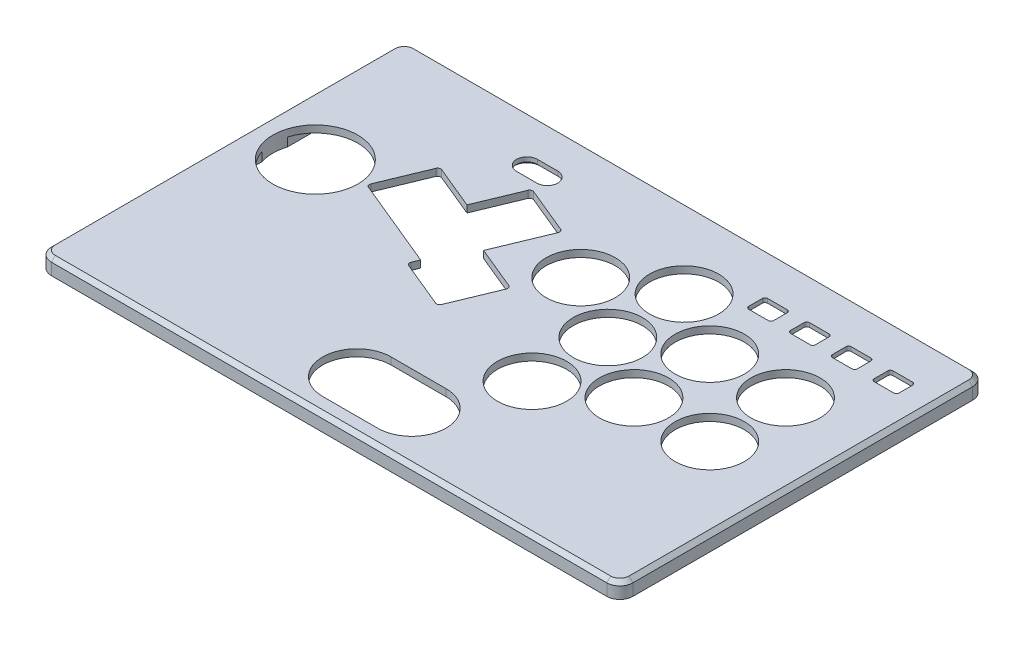
SolidWorks part; units mm, degrees
ref_plane "Front Plane" through (0, 0, 0) normal (0, 0, 1) x (1, 0, 0)
ref_plane "Top Plane" through (0, 0, 0) normal (0, 1, 0) x (1, 0, 0)
ref_plane "Right Plane" through (0, 0, 0) normal (1, 0, 0) x (0, 0, -1)
sketch "Sketch1" plane through (0, 0, 0) normal (0, 1, 0) x (1, 0, 0)
  line L1 (0, 0) -> (222.53, 0)
  line L2 (0, 0) -> (0, 140)
  line L3 (0, 140) -> (222.53, 140)
  line L4 (222.53, 0) -> (222.53, 140)
  line L5 (217.53, 140) -> (50.88, 140) construction
  line L6 (222.53, 5) -> (222.53, 135) construction
extrude "Top Plate" add sketch "Sketch1" along normal blind 6
fillet "Corner Fillet" radius 5 4 edges at (0, 3, -140) (0, 3, 0) (222.53, 3, -140) (222.53, 3, 0)
hole_wizard "M3 Clearance Hole1" positions "3DSketch1" profile "Sketch3" hole size "M3" standard "ANSI Metric"
sketch3d "3DSketch1"
  line L0 (5, 0, 0) -> (217.53, 0, 0) construction
  line L1 (222.53, 0, -5) -> (222.53, 0, -135) construction
  line L2 (217.53, 0, -140) -> (5, 0, -140) construction
  line L3 (0, 0, -135) -> (0, 0, -5) construction
  point P0 (217.03, 0, -5.5)
  point P2 (217.03, 0, -134.5)
  point P4 (5.5, 0, -134.5)
  point P6 (5.5, 0, -5.5)
  dimension "D1" = 5.5
  dimension "D2" = 5.5
  dimension "D3" = 5.5
  dimension "D4" = 5.5
  dimension "D5" = 5.5
  dimension "D6" = 5.5
  dimension "D7" = 5.5
  dimension "D8" = 5.5
sketch "Sketch3" plane through (217.03, 0, -5.5) normal (1, 0, 0) x (0, 0, -1)
  line L0 (0, 0) -> (0, 5.25)
  line L1 (0, 5.25) -> (1.7, 4.2285)
  line L2 (1.7, 4.2285) -> (1.7, 0)
  line L5 (1.7, 0) -> (0, 0)
  line L10 (0, 5.25) -> (-1.7, 4.2285) construction
  line L11 (0, -6.35) -> (0, 107.95) construction
  dimension "Hole Dia." = 3.4
  dimension "Hole Depth" = 5.25
  dimension "Drill Angle" = 118
sketch "Sketch4" plane through (0, 6, 0) normal (0, -1, 0) x (-1, 0, 0)
  line L0 (-94.0588, 59.555) -> (-76.4589, 66.8451) construction
  line L1 (-94.0588, 59.555) -> (-101.349, 77.1549) construction
  line L2 (-76.4589, 66.8451) -> (-77.9897, 70.5406) construction
  line L3 (-101.349, 77.1549) -> (-83.7491, 84.445) construction
  line L4 (-94.0588, 59.555) -> (-83.7491, 84.445) construction
  line L5 (-76.4589, 66.8451) -> (-101.349, 77.1549) construction
  line L6 (-77.9897, 70.5406) -> (-60.3898, 77.8307) construction
  line L7 (-83.7491, 84.445) -> (-85.2798, 88.1405) construction
  line L8 (-60.3898, 77.8307) -> (-67.6799, 95.4306) construction
  line L9 (-85.2798, 88.1405) -> (-67.6799, 95.4306) construction
  line L10 (-77.9897, 70.5406) -> (-67.6799, 95.4306) construction
  line L11 (-60.3898, 77.8307) -> (-85.2798, 88.1405) construction
  line L12 (-60.3898, 77.8307) -> (-42.7899, 85.1209) construction
  line L14 (-42.7899, 85.1209) -> (-50.08, 102.7208) construction
  line L15 (-67.6799, 95.4306) -> (-50.08, 102.7208) construction
  line L16 (-60.3898, 77.8307) -> (-50.08, 102.7208) construction
  line L17 (-42.7899, 85.1209) -> (-67.6799, 95.4306) construction
  line L19 (-67.6799, 95.4306) -> (-74.97, 113.0306) construction
  line L20 (-85.2798, 88.1405) -> (-92.5699, 105.7404) construction
  line L21 (-74.97, 113.0306) -> (-92.5699, 105.7404) construction
  line L22 (-67.6799, 95.4306) -> (-92.5699, 105.7404) construction
  line L23 (-85.2798, 88.1405) -> (-74.97, 113.0306) construction
  line L24 (-5, 0) -> (-217.53, 0) construction
  line L25 (-59.9305, 76.7221) -> (-42.3306, 84.0122)
  line L26 (-41.6812, 85.5801) -> (-48.9713, 103.18)
  line L27 (-67.0304, 96.9985) -> (-50.5392, 103.8294)
  line L28 (-67.0304, 96.9985) -> (-73.8613, 113.4898)
  line L29 (-75.4292, 114.1392) -> (-93.0291, 106.8491)
  line L30 (-86.3884, 87.6813) -> (-93.6786, 105.2812)
  line L31 (-85.3169, 85.0944) -> (-86.3884, 87.6813)
  line L32 (-101.8082, 78.2635) -> (-85.3169, 85.0944)
  line L33 (-95.1675, 59.0958) -> (-102.4576, 76.6957)
  line L34 (-93.5996, 58.4463) -> (-75.9997, 65.7365)
  line L35 (-75.3503, 67.3043) -> (-76.4218, 69.8912)
  line L36 (-76.4218, 69.8912) -> (-59.9305, 76.7221)
  line L37 (-66.5712, 95.8899) -> (-74.3206, 114.5984) construction
  line L38 (-68.1391, 96.5393) -> (-49.4305, 104.2886) construction
  line L39 (-74.3206, 114.5984) -> (-94.1378, 106.3899) construction
  line L40 (-86.3884, 87.6813) -> (-94.1378, 106.3899) construction
  line L41 (-102.9168, 77.8043) -> (-85.3169, 85.0944) construction
  line L42 (-94.7083, 57.9871) -> (-102.9168, 77.8043) construction
  line L43 (-94.7083, 57.9871) -> (-74.8911, 66.1957) construction
  line L44 (-74.8911, 66.1957) -> (-76.4218, 69.8912) construction
  line L45 (-59.9305, 76.7221) -> (-41.222, 84.4714) construction
  line L46 (-41.222, 84.4714) -> (-49.4305, 104.2886) construction
  line L47 (-123.9039, 19) -> (-102.9039, 19) construction
  line L48 (-123.9039, 32.1) -> (-102.9039, 32.1)
  line L49 (-123.9039, 5.9) -> (-102.9039, 5.9)
  circle A0 centre (-23, 83.0083) radius 16.25
  circle A1 centre (-137.9339, 51) radius 13.25
  circle A2 centre (-162.9339, 65) radius 13.25
  circle A3 centre (-191.9339, 65) radius 13.25
  circle A4 centre (-191.9339, 94) radius 13.25
  circle A5 centre (-162.9339, 94) radius 13.25
  circle A6 centre (-137.9339, 80) radius 13.25
  circle A7 centre (-138.1143, 108.9994) radius 13.25
  circle A8 centre (-112.9159, 94.6459) radius 13.25
  arc A9 (-93.0291, 106.8491) -> (-93.6786, 105.2812) centre (-92.5699, 105.7404) ccw
  arc A10 (-101.8082, 78.2635) -> (-102.4576, 76.6957) centre (-101.349, 77.1549) ccw
  arc A11 (-95.1675, 59.0958) -> (-93.5996, 58.4463) centre (-94.0588, 59.555) ccw
  arc A12 (-75.9997, 65.7365) -> (-75.3503, 67.3043) centre (-76.4589, 66.8451) ccw
  arc A13 (-42.3306, 84.0122) -> (-41.6812, 85.5801) centre (-42.7899, 85.1209) ccw
  arc A14 (-73.8613, 113.4898) -> (-75.4292, 114.1392) centre (-74.97, 113.0306) ccw
  arc A15 (-48.9713, 103.18) -> (-50.5392, 103.8294) centre (-50.08, 102.7208) ccw
  arc A16 (-123.9039, 32.1) -> (-123.9039, 5.9) centre (-123.9039, 19) ccw
  arc A17 (-102.9039, 5.9) -> (-102.9039, 32.1) centre (-102.9039, 19) ccw
  point P28 (-88.9039, 72)
  point P29 (-72.8348, 82.9856)
  point P30 (-55.2349, 90.2758)
  point P35 (-80.1249, 100.5855)
  point P90 (-113.4039, 19)
  point P96 (-89.8039, 19)
  point P97 (-137.0039, 19)
  dimension "D1" = 32.5
  dimension "D2" = 26.5
  dimension "D6" = 1.2
  dimension "D8" = 13.1
  dimension "D3" = 22.5
  dimension "D4" = 19.05
  dimension "D5" = 1.2
  dimension "D7" = 47.2
extrude "Primary Buttons" cut sketch "Sketch4" along normal blind 10 contours A15 L26 A13 L25 L36 L35 A12 L34 A11 L33 A10 L32 L31 L30 A9 L29 A14 L28 L27 | A0 | A8 | A7 | A5 | A4 | A6 | A1 | A2 | A3 | A17 L49 A16 L48 region at (74.3536, 6, -86.5154) region at (113.4039, 6, -19) region at (23, 6, -83.0083) region at (137.9339, 6, -51) region at (162.9339, 6, -65) region at (191.9339, 6, -65) region at (191.9339, 6, -94) region at (162.9339, 6, -94) region at (137.9339, 6, -80) region at (138.1143, 6, -108.9994) region at (112.9159, 6, -94.6459)
sketch "Sketch5" plane through (0, 0, 0) normal (0, -1, 0) x (1, 0, 0)
  line L2 (154.55, -122.52) -> (154.55, -117.32)
  line L3 (155.55, -116.32) -> (163.05, -116.32)
  line L4 (164.05, -122.52) -> (164.05, -117.32)
  line L5 (154.55, -123.52) -> (164.05, -116.32) construction
  line L6 (154.55, -116.32) -> (164.05, -123.52) construction
  line L7 (155.55, -123.52) -> (163.05, -123.52)
  line L8 (170.55, -122.52) -> (170.55, -117.32)
  line L9 (171.55, -116.32) -> (179.05, -116.32)
  line L10 (180.05, -122.52) -> (180.05, -117.32)
  line L11 (171.55, -123.52) -> (179.05, -123.52)
  line L12 (170.55, -123.52) -> (180.05, -116.32) construction
  line L13 (170.55, -116.32) -> (180.05, -123.52) construction
  line L14 (186.55, -122.52) -> (186.55, -117.32)
  line L15 (187.55, -116.32) -> (195.05, -116.32)
  line L16 (196.05, -122.52) -> (196.05, -117.32)
  line L17 (187.55, -123.52) -> (195.05, -123.52)
  line L18 (186.55, -123.52) -> (196.05, -116.32) construction
  line L19 (186.55, -116.32) -> (196.05, -123.52) construction
  line L20 (202.55, -122.52) -> (202.55, -117.32)
  line L21 (203.55, -116.32) -> (211.05, -116.32)
  line L22 (212.05, -122.52) -> (212.05, -117.32)
  line L23 (203.55, -123.52) -> (211.05, -123.52)
  line L24 (202.55, -123.52) -> (212.05, -116.32) construction
  line L25 (202.55, -116.32) -> (212.05, -123.52) construction
  line L26 (159.3, -119.92) -> (160, -119.92) construction
  arc A0 (163.05, -123.52) -> (164.05, -122.52) centre (163.05, -122.52) ccw
  arc A1 (155.55, -123.52) -> (154.55, -122.52) centre (155.55, -122.52) cw
  arc A2 (154.55, -117.32) -> (155.55, -116.32) centre (155.55, -117.32) cw
  arc A3 (163.05, -116.32) -> (164.05, -117.32) centre (163.05, -117.32) cw
  arc A4 (179.05, -123.52) -> (180.05, -122.52) centre (179.05, -122.52) ccw
  arc A5 (171.55, -123.52) -> (170.55, -122.52) centre (171.55, -122.52) cw
  arc A6 (170.55, -117.32) -> (171.55, -116.32) centre (171.55, -117.32) cw
  arc A7 (179.05, -116.32) -> (180.05, -117.32) centre (179.05, -117.32) cw
  arc A8 (195.05, -123.52) -> (196.05, -122.52) centre (195.05, -122.52) ccw
  arc A9 (187.55, -123.52) -> (186.55, -122.52) centre (187.55, -122.52) cw
  arc A10 (186.55, -117.32) -> (187.55, -116.32) centre (187.55, -117.32) cw
  arc A11 (195.05, -116.32) -> (196.05, -117.32) centre (195.05, -117.32) cw
  arc A12 (211.05, -123.52) -> (212.05, -122.52) centre (211.05, -122.52) ccw
  arc A13 (203.55, -123.52) -> (202.55, -122.52) centre (203.55, -122.52) cw
  arc A14 (202.55, -117.32) -> (203.55, -116.32) centre (203.55, -117.32) cw
  arc A15 (211.05, -116.32) -> (212.05, -117.32) centre (211.05, -117.32) cw
  point P0 (159.3, -119.92)
  point P7 (175.3, -119.92)
  point P39 (191.3, -119.92)
  point P56 (207.3, -119.92)
  dimension "D1" = 7.2
  dimension "D3" = 1
  dimension "D2" = 9.5
  dimension "D5" = 16
  dimension "D6" = 0.7
  dimension "D4" = 4
extrude "Extra Buttons" cut sketch "Sketch5" against normal up to next
sketch "Sketch8" plane through (0, 0, 0) normal (0, -1, 0) x (1, 0, 0)
  line L24 (215.03, -132.5) -> (215.03, -7.5)
  line L25 (7.5, -132.5) -> (215.03, -132.5)
  line L26 (7.5, -7.5) -> (7.5, -132.5)
  line L27 (215.03, -7.5) -> (7.5, -7.5)
  line L28 (215.03, -132.5) -> (215.03, -7.5)
  line L29 (7.5, -132.5) -> (215.03, -132.5)
  line L30 (7.5, -7.5) -> (7.5, -132.5)
  line L31 (215.03, -7.5) -> (7.5, -7.5)
  dimension "D1" = 7.5
extrude "Hollow Out" cut sketch "Sketch8" against normal blind 3.3
fillet "Fillet1" radius 10 3 edges at (7.5, 1.65, -132.5) (7.5, 1.65, -7.5) (215.03, 1.65, -7.5)
fillet "Fillet2" radius 5 1 edges at (215.03, 1.65, -132.5)
sketch "Sketch15" plane through (0, 0, 0) normal (0, -1, 0) x (1, 0, 0)
  line L0 (163.05, -116.32) -> (155.55, -116.32) construction
  line L1 (151.3, -127.92) -> (215.3, -127.92)
  line L2 (151.3, -127.92) -> (151.3, -111.92)
  line L3 (151.3, -111.92) -> (215.3, -111.92)
  line L4 (215.3, -127.92) -> (215.3, -111.92)
  line L5 (154.55, -117.32) -> (154.55, -122.52) construction
  line L6 (211.05, -116.32) -> (203.55, -116.32) construction
  point P4 (159.3, -119.92)
  point P5 (207.3, -119.92)
  point P10 (159.3, -116.32)
  point P13 (154.55, -119.92)
  point P18 (207.3, -116.32)
  dimension "D1" = 8
  dimension "D2" = 8
  dimension "D3" = 8
  dimension "D4" = 8
extrude "Cut-Extrude4" cut sketch "Sketch15" against normal blind 4.4
sketch "Sketch9" plane through (0, 6, 0) normal (0, 1, 0) x (1, 0, 0)
  line L0 (68.26, 121.5875) -> (70.35, 121.5875) construction
  line L1 (70.6, 121.1545) -> (70.1, 122.0205) construction
  line L2 (68.51, 122.0205) -> (68.01, 121.1545) construction
  line L3 (65.42, 121.5875) -> (73.19, 121.5875) construction
  line L4 (65.42, 125.5875) -> (73.19, 125.5875)
  line L5 (65.42, 117.5875) -> (73.19, 117.5875)
  arc A0 (65.42, 125.5875) -> (65.42, 117.5875) centre (65.42, 121.5875) ccw
  arc A1 (73.19, 117.5875) -> (73.19, 125.5875) centre (73.19, 121.5875) ccw
  point P8 (69.305, 121.5875)
  dimension "D2" = 4
  dimension "D1" = 7.77
extrude "Light Guide Cutout" cut sketch "Sketch9" against normal blind 10
chamfer "Chamfer1" distance 1 angle 45 4 edges at (77.19, 3.3, -121.5875) (69.305, 3.3, -117.5875) (61.42, 3.3, -121.5875) (69.305, 3.3, -125.5875)
chamfer "Top Chamfer" distance 1.5 angle 45 8 edges at (221.0655, 6, -138.5355) (222.53, 6, -70) (221.0655, 6, -1.4645) (111.265, 6, -140) (1.4645, 6, -138.5355) (0, 6, -70) (1.4645, 6, -1.4645) (111.265, 6, 0)
sketch "Sketch11" plane through (0, 0, 0) normal (0, -1, 0) x (1, 0, 0)
  line L0 (217.03, -138.6012) -> (212.9288, -134.5)
  line L1 (217.03, -138.6012) -> (221.1312, -134.5)
  line L2 (212.9288, -134.5) -> (217.03, -130.3988)
  line L3 (221.1312, -134.5) -> (217.03, -130.3988)
  line L4 (217.03, -138.6012) -> (217.03, -130.3988) construction
  line L5 (212.9288, -134.5) -> (221.1312, -134.5) construction
  line L6 (1.3988, -134.5) -> (5.5, -130.3988)
  line L7 (1.3988, -134.5) -> (5.5, -138.6012)
  line L8 (5.5, -130.3988) -> (9.6012, -134.5)
  line L9 (5.5, -138.6012) -> (9.6012, -134.5)
  line L10 (1.3988, -134.5) -> (9.6012, -134.5) construction
  line L11 (5.5, -130.3988) -> (5.5, -138.6012) construction
  line L12 (5.5, -9.6012) -> (1.3988, -5.5)
  line L13 (5.5, -9.6012) -> (9.6012, -5.5)
  line L14 (1.3988, -5.5) -> (5.5, -1.3988)
  line L15 (9.6012, -5.5) -> (5.5, -1.3988)
  line L16 (5.5, -9.6012) -> (5.5, -1.3988) construction
  line L17 (1.3988, -5.5) -> (9.6012, -5.5) construction
  line L18 (217.03, -9.6012) -> (212.9288, -5.5)
  line L19 (217.03, -9.6012) -> (221.1312, -5.5)
  line L20 (212.9288, -5.5) -> (217.03, -1.3988)
  line L21 (221.1312, -5.5) -> (217.03, -1.3988)
  line L22 (217.03, -9.6012) -> (217.03, -1.3988) construction
  line L23 (212.9288, -5.5) -> (221.1312, -5.5) construction
  line L24 (217.53, -140) -> (5, -140) construction
  point P1 (217.03, -134.5)
  point P2 (5.5, -134.5)
  point P3 (5.5, -5.5)
  point P8 (217.03, -5.5)
  dimension "D1" = 45
  dimension "D2" = 5.8
extrude "Nut Cutout" cut sketch "Sketch11" against normal blind 2 from offset 1.2 offset against normal yes
sketch "Sketch16" plane through (0, 0, 0) normal (0, -1, 0) x (1, 0, 0)
  line L0 (217.53, -140) -> (5, -140) construction
  line L1 (90, -111) -> (118, -111)
  line L2 (90, -111) -> (90, -131)
  line L3 (90, -131) -> (132.53, -131)
  line L8 (118, -111) -> (132.53, -131)
  line L11 (0, -135) -> (0, -5) construction
  line L12 (222.53, -5) -> (222.53, -135) construction
  dimension "D1" = 9
  dimension "D2" = 90
  dimension "D3" = 90
  dimension "D4" = 20
  dimension "D5" = 28
extrude "Host USB Cutout" [suppressed] cut sketch "Sketch16" against normal blind 3.5
chamfer "Chamfer4" [suppressed] distance 2 angle 45
fillet "Top Fillet" [suppressed] radius 1.5
sketch "Sketch17" plane through (0, 6, 0) normal (0, 1, 0) x (1, 0, 0)
  line L1 (1.5, 135) -> (5, 135)
  line L2 (1.5, 135) -> (1.5, 140)
  line L3 (1.5, 140) -> (5, 140)
  line L4 (5, 135) -> (5, 140)
  line L5 (1.5, 140) -> (41.5, 140)
  line L6 (1.5, 140) -> (1.5, 180)
  line L7 (1.5, 180) -> (41.5, 180)
  line L8 (41.5, 140) -> (41.5, 180)
  line L9 (1.5, 5) -> (5, 5)
  line L10 (1.5, 5) -> (1.5, 0)
  line L11 (1.5, 0) -> (5, 0)
  line L12 (5, 5) -> (5, 0)
  line L13 (1.5, 0) -> (41.5, 0)
  line L14 (1.5, 0) -> (1.5, -40)
  line L15 (1.5, -40) -> (41.5, -40)
  line L16 (41.5, 0) -> (41.5, -40)
  line L17 (221.03, 5) -> (217.53, 5)
  line L18 (221.03, 5) -> (221.03, 0)
  line L19 (221.03, 0) -> (217.53, 0)
  line L20 (217.53, 5) -> (217.53, 0)
  line L21 (221.03, 0) -> (181.03, 0)
  line L22 (221.03, 0) -> (221.03, -40)
  line L23 (221.03, -40) -> (181.03, -40)
  line L24 (181.03, 0) -> (181.03, -40)
  line L25 (221.03, 135) -> (217.53, 135)
  line L26 (221.03, 135) -> (221.03, 140)
  line L27 (221.03, 140) -> (217.53, 140)
  line L28 (217.53, 135) -> (217.53, 140)
  line L29 (221.03, 140) -> (181.03, 140)
  line L30 (221.03, 140) -> (221.03, 180)
  line L31 (221.03, 180) -> (181.03, 180)
  line L32 (181.03, 140) -> (181.03, 180)
  dimension "D1" = 40
  dimension "D2" = 5
extrude "top Build plate adhesion" [suppressed] add sketch "Sketch17" against normal blind 0.6 contours L21 L24 L23 L22 L19 | L16 L13 L11 L14 L15 | L12 L9 L10 L11 | L17 L20 L19 L18 | L5 L8 L7 L6 L3 | L32 L29 L27 L30 L31 | L28 L25 L26 L27 | L1 L4 L3 L2
fillet "Fillet3" [suppressed] radius 20
sketch "Sketch18" plane through (0, 0, 0) normal (0, -1, 0) x (1, 0, 0)
  line L0 (217.53, -140) -> (5, -140) construction
  line L1 (0, -5) -> (2, -5)
  line L2 (0, -5) -> (0, 1)
  line L3 (0, 1) -> (5, 1)
  line L4 (5, -2) -> (5, 1)
  line L5 (222.53, -5) -> (220.53, -5)
  line L6 (222.53, -5) -> (222.53, 1)
  line L7 (222.53, 1) -> (217.53, 1)
  line L8 (217.53, -2) -> (217.53, 1)
  line L9 (222.53, -135) -> (217.53, -135)
  line L10 (222.53, -135) -> (222.53, -141)
  line L11 (222.53, -141) -> (214.53, -141)
  line L12 (214.53, -138) -> (214.53, -141)
  line L13 (0, -135) -> (5, -135)
  line L14 (0, -135) -> (0, -141)
  line L15 (0, -141) -> (8, -141)
  line L16 (8, -138) -> (8, -141)
  line L17 (0, 1) -> (40, 1)
  line L18 (0, 1) -> (0, 41)
  line L19 (0, 41) -> (40, 41)
  line L20 (40, 1) -> (40, 41)
  line L21 (222.53, 1) -> (182.53, 1)
  line L22 (222.53, 1) -> (222.53, 41)
  line L23 (222.53, 41) -> (182.53, 41)
  line L24 (182.53, 1) -> (182.53, 41)
  line L25 (222.53, -141) -> (182.53, -141)
  line L26 (222.53, -141) -> (222.53, -181)
  line L27 (222.53, -181) -> (182.53, -181)
  line L28 (182.53, -141) -> (182.53, -181)
  line L29 (0, -141) -> (40, -141)
  line L30 (0, -141) -> (0, -181)
  line L31 (0, -181) -> (40, -181)
  line L32 (40, -141) -> (40, -181)
  arc A0 (220.53, -5) -> (217.53, -2) centre (220.53, -2) cw
  arc A1 (2, -5) -> (5, -2) centre (2, -2) ccw
  arc A2 (5, -135) -> (8, -138) centre (5, -138) cw
  arc A3 (217.53, -135) -> (214.53, -138) centre (217.53, -138) ccw
  arc M49 (0, -135) -> (5, -140) centre (5, -135) ccw
  line M50 (5, -140) -> (217.53, -140)
  arc M51 (217.53, -140) -> (222.53, -135) centre (217.53, -135) ccw
  dimension "D4" = 3
  dimension "D1" = 40
  dimension "D2" = 5
  dimension "D3" = 1
extrude "Boss-Extrude1" [suppressed] add sketch "Sketch18" against normal blind 0.6 contours L25 L28 L27 L26 L11 | L32 L29 L15 L30 L31 | L16 L14 L15 M50 M49 | L12 L11 L10 M50 M51 | L24 L21 L7 L22 L23 | L17 L20 L19 L18 L3 | L3 L4 A1 L1 L2 | L7 L8 A0 L5 L6
fillet "Fillet4" [suppressed] radius 20
